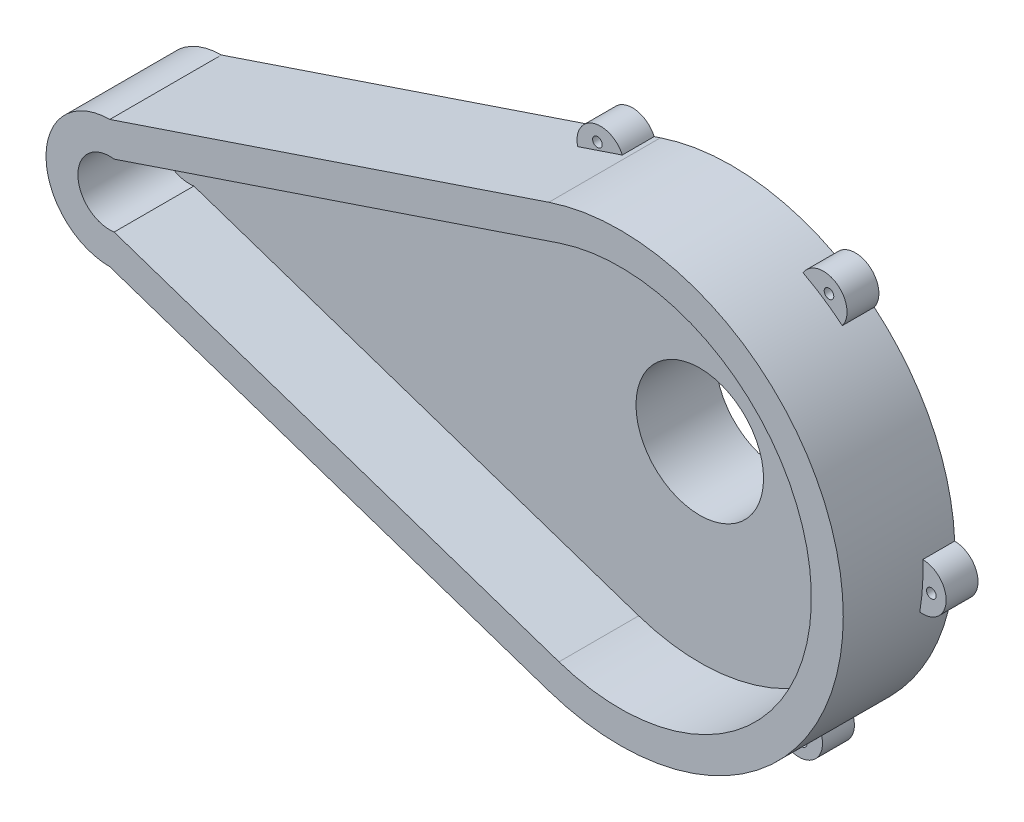
SolidWorks part; units mm, degrees
ref_plane "Front Plane" through (0, 0, 0) normal (0, 0, 1) x (1, 0, 0)
ref_plane "Top Plane" through (0, 0, 0) normal (0, 1, 0) x (1, 0, 0)
ref_plane "Right Plane" through (0, 0, 0) normal (1, 0, 0) x (0, 0, -1)
sketch "Sketch1" plane through (0, 0, 0) normal (0, 0, 1) x (1, 0, 0)
  line L0 (-100.2662, 20) -> (37.4015, 66.3421)
  line L1 (-100.2662, -20) -> (37.4015, -66.3421)
  arc A0 (-100.2662, 20) -> (-100.2662, -20) centre (-100.2662, 0) ccw
  arc A1 (37.4015, -66.3421) -> (37.4015, 66.3421) centre (59.7338, 0) ccw
  point P4 (-120.2662, 0)
  point P5 (129.7338, 0)
  dimension "D1" = 160
  dimension "D2" = 40
  dimension "D3" = 140
extrude "Boss-Extrude1" add sketch "Sketch1" against normal blind 35
sketch "Sketch2" plane through (0, 0, 0) normal (0, 0, 1) x (1, 0, 0)
  line L0 (-100.2662, -20) -> (37.4015, -66.3421) construction
  line L1 (37.4015, 66.3421) -> (-100.2662, 20) construction
  line L2 (-100.2662, -20) -> (37.4015, -66.3421)
  line L3 (37.4015, 66.3421) -> (-100.2662, 20)
  line L4 (40.5918, 56.8646) -> (-98.9049, 9.9069)
  line L5 (-98.9049, -9.9069) -> (40.5918, -56.8646)
  arc A0 (37.4015, -66.3421) -> (37.4015, 66.3421) centre (59.7338, 0) ccw construction
  arc A1 (-100.2662, 20) -> (-100.2662, -20) centre (-100.2662, 0) ccw construction
  arc A2 (37.4015, -66.3421) -> (37.4015, 66.3421) centre (59.7338, 0) ccw
  arc A3 (-100.2662, 20) -> (-100.2662, -20) centre (-100.2662, 0) ccw
  arc A4 (40.5918, -56.8646) -> (40.5918, 56.8646) centre (59.7338, 0) ccw
  arc A5 (-98.9049, 9.9069) -> (-98.9049, -9.9069) centre (-100.2662, 0) ccw
  dimension "D1" = 10
extrude "Cut-Extrude1" cut sketch "Sketch2" against normal blind 25 contours A4 L4 A5 L5
sketch "Sketch3" plane through (0, 0, -35) normal (0, 0, -1) x (-1, 0, 0)
  line L0 (100.2662, 24.4949) -> (100.2662, 35)
  line L3 (90.2662, 30.3194) -> (90.2662, 35)
  line L5 (90.2662, -27.5224) -> (90.2662, -35)
  line L7 (100.2662, -24.4949) -> (100.2662, -35)
  line L8 (100.2662, 20) -> (-37.4015, 66.3421)
  line L9 (123.1791, -5) -> (134.6312, -5)
  line L10 (123.1791, 5) -> (134.6312, 5)
  line L11 (-37.4015, -66.3421) -> (100.2662, -20)
  line L15 (100.2662, 20) -> (83.4535, 25.6595)
  line L16 (86.0033, -24.8012) -> (100.2662, -20)
  arc A0 (90.2662, 35) -> (100.2662, 35) centre (95.2662, 35) cw
  arc A1 (90.2662, -35) -> (100.2662, -35) centre (95.2662, -35) ccw
  arc A4 (134.6312, 5) -> (134.6312, -5) centre (134.6312, 0) cw
  arc A6 (104.2662, 19.5959) -> (100.2662, 24.4949) centre (105.2662, 24.4949) cw
  arc A7 (100.2662, -24.4949) -> (104.2662, -19.5959) centre (105.2662, -24.4949) cw
  arc A8 (90.2662, -27.5224) -> (86.0033, -24.8012) centre (87.2662, -27.5224) ccw
  arc A9 (118.5965, 8) -> (123.1791, 5) centre (123.1791, 10) ccw
  arc A10 (104.2662, 19.5959) -> (100.2662, 20) centre (100.2662, 0) ccw
  arc A11 (118.5965, -8) -> (118.5965, 8) centre (100.2662, 0) ccw
  arc A14 (118.5965, -8) -> (123.1791, -5) centre (123.1791, -10) cw
  arc A15 (83.4535, 25.6595) -> (90.2662, 30.3194) centre (85.2662, 30.3194) ccw
  arc A16 (100.2662, -20) -> (100.2662, 20) centre (100.2662, 0) ccw
  arc A17 (-37.4015, 66.3421) -> (-37.4015, -66.3421) centre (-59.7338, 0) ccw
  arc A18 (100.2662, -20) -> (104.2662, -19.5959) centre (100.2662, 0) ccw
  dimension "D1" = 10
  dimension "D2" = 5
  dimension "D6" = 5
  dimension "D7" = 5
  dimension "D8" = 5
  dimension "D10" = 3
  dimension "D4" = 5
  dimension "D5" = 5
  dimension "D3" = 5
  dimension "D9" = 0
extrude "Boss-Extrude2" add sketch "Sketch3" against normal blind 35 rebuild error yes
ref_plane "Plane1" through (0, 0, -50) normal (0, 0, 1) x (1, 0, 0)
sketch "Sketch6" plane through (0, 0, -50) normal (0, 0, 1) x (1, 0, 0)
  circle A0 centre (59.7338, 0) radius 45
  dimension "D1" = 90
sketch "Sketch9" plane through (0, 0, -35) normal (0, 0, -1) x (-1, 0, 0)
  circle A0 centre (-59.7338, 0) radius 70
loft "Loft2" add profiles "Sketch9", "Sketch6" connector at (-0.3157, 35.973, -35) connector at (22.8521, 25.7826, -50)
sketch "Sketch10" plane through (0, 0, -35) normal (0, 0, -1) x (-1, 0, 0)
  circle A1 centre (95.2662, 35) radius 2.5
  circle A2 centre (95.2662, -35) radius 2.5
  circle A3 centre (134.6312, 0) radius 2.5
  dimension "D1" = 5
  dimension "D2" = 5
  dimension "D3" = 5
extrude "Cut-Extrude3" cut sketch "Sketch10" against normal blind 86 rebuild error yes
sketch "Sketch11" plane through (0, 0, -50) normal (0, 0, -1) x (-1, 0, 0)
  circle A0 centre (-59.7338, 0) radius 20
  dimension "D1" = 40
extrude "Cut-Extrude4" cut sketch "Sketch11" against normal blind 120
sketch "Sketch12" plane through (0, 0, -35) normal (0, 0, -1) x (-1, 0, 0)
  circle A0 centre (100.2662, 0) radius 9.545
  dimension "D1" = 19.09
extrude "Cut-Extrude5" cut sketch "Sketch12" against normal blind 5
sketch "Sketch13" plane through (0, 0, -35) normal (0, 0, -1) x (-1, 0, 0)
  arc A2 (-92.1369, 62.0487) -> (-104.442, 53.8625) centre (-98.5061, 58.2813) ccw
  arc A3 (-37.4015, 66.3421) -> (-37.4015, -66.3421) centre (-59.7338, 0) ccw construction
  arc A4 (-92.1369, 62.0487) -> (-104.442, 53.8625) centre (-59.7338, 0) ccw
  circle A5 centre (-100.2546, 60.453) radius 1.5
  dimension "D1" = 3
  dimension "D2" = 7.4
  dimension "D3" = 98.5061
extrude "Boss-Extrude4" add sketch "Sketch13" against normal blind 10
pattern_circular "CirPattern1" count 6 over 360 about axis through (59.7338, 0, -35) along (0, 0, 1) of "Boss-Extrude4"
sketch "Sketch14" plane through (0, 0, -35) normal (0, 0, -1) x (-1, 0, 0)
  circle A1 centre (-60, 36) radius 3.1
  dimension "D1" = 36
  dimension "D2" = 60
  dimension "D3" = 6.2
extrude "Cut-Extrude6" cut sketch "Sketch14" along normal blind 65
pattern_circular "CirPattern2" count 5 over 360 about axis through (59.7338, 0, -50) along (0, 0, 1) of "Cut-Extrude6"
sketch "Sketch15" plane through (0, 0, -50) normal (0, 0, -1) x (-1, 0, 0)
  circle A2 centre (-94.0541, 10.8714) radius 5.1
  arc A3 (-96.4933, 6.3926) -> (-93.4697, 15.9378) centre (-94.0541, 10.8714) ccw
  circle A23 centre (-60, 36) radius 5.1
  arc A24 (-65.0134, 36.9358) -> (-55.001, 37.0099) centre (-60, 36) ccw
  circle A26 centre (-25.578, 11.3778) radius 5.1
  arc A27 (-26.2372, 16.435) -> (-23.0728, 6.9355) centre (-25.578, 11.3778) ccw
  circle A29 centre (-38.3581, -28.9681) radius 5.1
  arc A30 (-33.7521, -26.7784) -> (-41.8088, -32.7235) centre (-38.3581, -28.9681) ccw
  circle A32 centre (-80.6786, -29.2811) radius 5.1
  arc A33 (-77.1728, -32.985) -> (-85.3165, -27.1598) centre (-80.6786, -29.2811) ccw
  arc A34 (-67.3608, 39.2661) -> (-95.0041, 18.868) centre (-59.7338, 0) ccw
  circle A35 centre (-59.7338, 0) radius 40
  arc A36 (-99.4349, 4.8802) -> (-88.5775, -27.7135) centre (-59.7338, 0) ccw
  arc A37 (-24.7463, 19.3876) -> (-52.6883, 39.3746) centre (-59.7338, 0) ccw
  arc A38 (-30.4833, -27.2839) -> (-20.1091, 5.4668) centre (-59.7338, 0) ccw
  arc A39 (-76.6434, -36.25) -> (-42.2898, -35.996) centre (-59.7338, 0) ccw
  circle A40 centre (-59.7338, 0) radius 45 construction
  circle A41 centre (-59.7338, 0) radius 45
  arc A42 (-93.4697, 15.9378) -> (-95.0041, 18.868) centre (-93.2406, 17.9246) cw
  arc A43 (-85.3165, -27.1598) -> (-88.5775, -27.7135) centre (-87.1353, -26.3279) cw
  arc A44 (-77.1728, -32.985) -> (-76.6434, -36.25) centre (-75.7979, -34.4375) ccw
  arc A45 (-41.8088, -32.7235) -> (-42.2898, -35.996) centre (-43.162, -34.1962) cw
  arc A46 (-33.7521, -26.7784) -> (-30.4833, -27.2839) centre (-31.9458, -25.9197) ccw
  arc A47 (-23.0728, 6.9355) -> (-20.1091, 5.4668) centre (-22.0903, 5.1935) cw
  arc A48 (-26.2372, 16.435) -> (-24.7463, 19.3876) centre (-26.4957, 18.4183) ccw
  arc A49 (-55.001, 37.0099) -> (-52.6883, 39.3746) centre (-53.0406, 37.4059) cw
  arc A50 (-65.0134, 36.9358) -> (-67.3608, 39.2661) centre (-66.9794, 37.3028) ccw
  arc A51 (-99.4349, 4.8802) -> (-96.4933, 6.3926) centre (-97.4499, 4.6361) cw
  point P29 (-80.2131, -34.3598)
  point P34 (-33.3841, -30.0948)
  point P39 (-22.9694, 15.7602)
  point P46 (-63.3618, 39.8351)
  dimension "D7" = 2
  dimension "D8" = 2
  dimension "D1" = 2
  dimension "D2" = 2
  dimension "D3" = 2
  dimension "D4" = 2
  dimension "D5" = 2
  dimension "D6" = 5
extrude "Boss-Extrude5" add sketch "Sketch15" along normal blind 1
sketch "Sketch16" plane through (0, 0, -51) normal (0, 0, -1) x (-1, 0, 0)
  circle A0 centre (-60, 36) radius 2.5
  circle A1 centre (-25.578, 11.3778) radius 2.5
  circle A2 centre (-38.3581, -28.9681) radius 2.5
  circle A3 centre (-80.6786, -29.2811) radius 2.5
  circle A4 centre (-94.0541, 10.8714) radius 2.5
  dimension "D1" = 5
  dimension "D2" = 5
  dimension "D3" = 5
  dimension "D4" = 5
  dimension "D5" = 5
extrude "Cut-Extrude7" cut sketch "Sketch16" against normal blind 10
